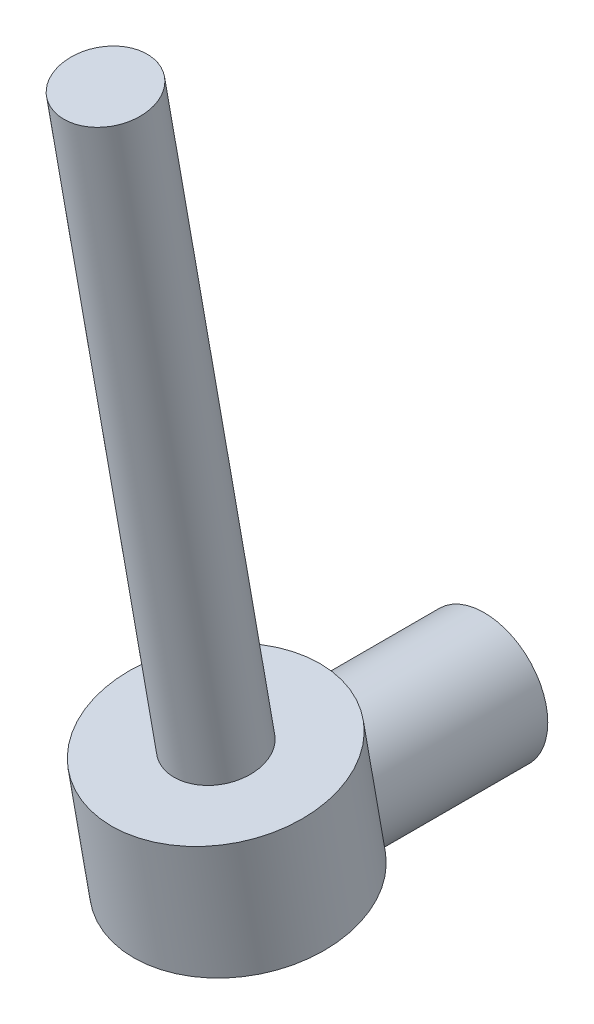
SolidWorks part; units mm, degrees
ref_plane "Front Plane" through (0, 0, 0) normal (0, 0, 1) x (1, 0, 0)
ref_plane "Top Plane" through (0, 0, 0) normal (0, 1, 0) x (1, 0, 0)
ref_plane "Right Plane" through (0, 0, 0) normal (1, 0, 0) x (0, 0, -1)
sketch "Sketch1" plane through (0, 0, 0) normal (0, 0, 1) x (1, 0, 0)
  circle A0 centre (0, 0) radius 30
  dimension "D1" = 60
extrude "Boss-Extrude1" add sketch "Sketch1" against normal blind 120
ref_axis "Axis2" through (-33, 0, 0) along (1, 0, 0)
ref_plane "Plane1" through (0, 0, 0) normal (0, 0.9848, 0.1736) x (1, 0, 0)
sketch "Sketch2" plane through (0, 0, 0) normal (0, 0.9848, 0.1736) x (1, 0, 0)
  circle A0 centre (0, 0) radius 50
  dimension "D1" = 100
extrude "Boss-Extrude2" add sketch "Sketch2" along normal blind 40 and the other way blind 20
sketch "Sketch3" plane through (0, 39.3923, 6.9459) normal (0, 0.9848, 0.1736) x (1, 0, 0)
  circle A0 centre (0, 0) radius 20
  dimension "D1" = 40
extrude "Boss-Extrude3" add sketch "Sketch3" along normal blind 300
